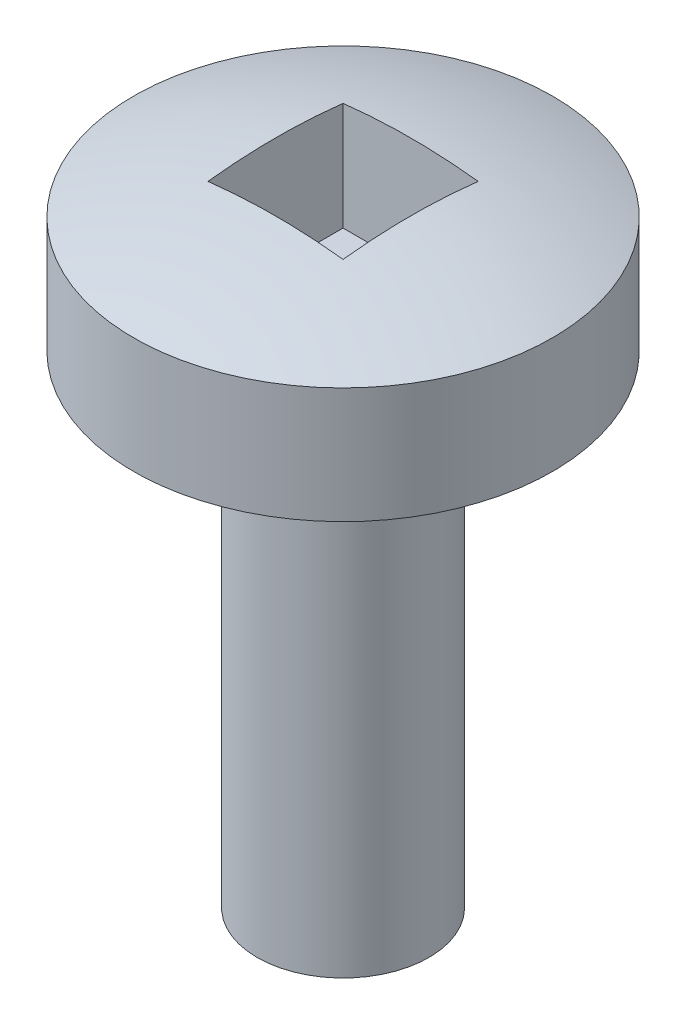
SolidWorks part; units mm, degrees
material "Cast Alloy Steel"
ref_plane "Front Plane" through (0, 0, 0) normal (0, 0, 1) x (1, 0, 0)
ref_plane "Top Plane" through (0, 0, 0) normal (0, 1, 0) x (1, 0, 0)
ref_plane "Right Plane" through (0, 0, 0) normal (1, 0, 0) x (0, 0, -1)
sketch "Sketch1" plane through (0, 0, 0) normal (0, 1, 0) x (1, 0, 0)
  circle A0 centre (0, 0) radius 1.1303
  dimension "D1" = 2.2606
extrude "threads" add sketch "Sketch1" against normal blind 6.35
sketch "Sketch2" plane through (0, 0, 0) normal (0, 1, 0) x (1, 0, 0)
  circle A0 centre (0, 0) radius 2.7559
  dimension "D1" = 5.5118
extrude "Head" add sketch "Sketch2" along normal blind 1.524
dome "HeadDome" faces to dome 1 distance 0.508 reverse direction no elliptical dome no face at (0, 1.524, 2.7559) parameters "D1"=0.508
ref_plane "DriverPlane" through (0, 2.032, 0) normal (0, 1, 0) x (1, 0, 0)
sketch "Sketch3" plane through (0, 2.032, 0) normal (0, 1, 0) x (1, 0, 0)
  line L1 (-0.889, -0.889) -> (0.889, -0.889)
  line L2 (-0.889, -0.889) -> (-0.889, 0.889)
  line L3 (-0.889, 0.889) -> (0.889, 0.889)
  line L4 (0.889, -0.889) -> (0.889, 0.889)
  line L5 (-0.889, -0.889) -> (0.889, 0.889) construction
  line L6 (-0.889, 0.889) -> (0.889, -0.889) construction
  point P0 (0, 0)
  dimension "D1" = 1.778
extrude "Driver" cut sketch "Sketch3" against normal blind 1.524
